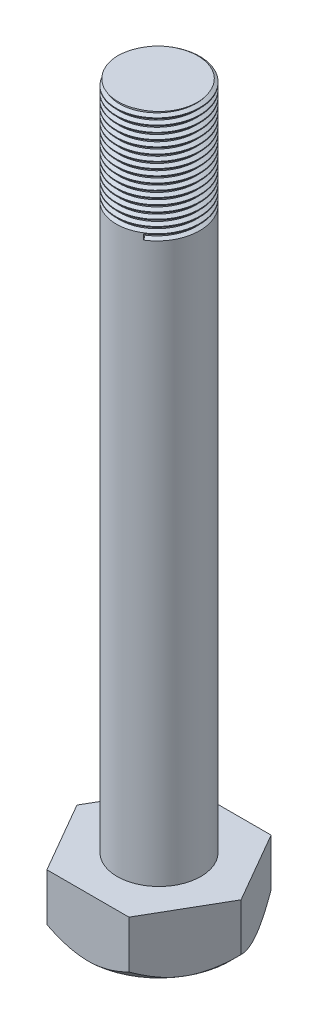
SolidWorks part; units mm, degrees
material "1.0143 (S275J0)"
ref_plane "Front Plane" through (0, 0, 0) normal (0, 0, 1) x (1, 0, 0)
ref_plane "Top Plane" through (0, 0, 0) normal (0, 1, 0) x (1, 0, 0)
ref_plane "Right Plane" through (0, 0, 0) normal (1, 0, 0) x (0, 0, -1)
sketch "Sketch1" plane through (0, 0, 0) normal (0, 1, 0) x (1, 0, 0)
  circle A0 centre (0, 0) radius 10
  dimension "D1" = 20
extrude "Boss-Extrude1" add sketch "Sketch1" along normal blind 160
sketch "Sketch2" plane through (0, 0, 0) normal (0, -1, 0) x (1, 0, 0)
  line L1 (19.6299, 0) -> (9.815, 17)
  line L2 (9.815, 17) -> (-9.815, 17)
  line L3 (-9.815, 17) -> (-19.6299, 0)
  line L4 (-19.6299, 0) -> (-9.815, -17)
  line L5 (-9.815, -17) -> (9.815, -17)
  line L6 (9.815, -17) -> (19.6299, 0)
  circle A0 centre (0, 0) radius 17 construction
  dimension "D1" = 34
extrude "Boss-Extrude2" add sketch "Sketch2" along normal blind 14
sketch "Sketch4" plane through (0, -14, 0) normal (0, -1, 0) x (1, 0, 0)
  circle A0 centre (0, 0) radius 17
extrude "Cut-Extrude1" cut sketch "Sketch4" against normal blind 14 draft 45 flip side to cut
thread "Thread1" pitch 1.5 method cut profile "Thread Profile1" start angle 0, offset 3, length 28, pitch 1.5, diameter 20
ref_plane "Plane1" through (-10, 163, 0) normal (0, 0, 1) x (-1, 0, 0)
sketch "Thread Profile1" plane through (-10, 163, 0) normal (0, 0, 1) x (-1, 0, 0)
  line L0 (0, 0) -> (0, 1.5) construction
  line L11 (0, 0) -> (0, 1.3125)
  line L12 (0, 1.3125) -> (-0.8119, 0.8437)
  line L13 (-0.8119, 0.8437) -> (-0.8119, 0.4687)
  line L15 (-0.8119, 0.4687) -> (0, 0)
  line L17 (-0.8119, 0.6562) -> (0, 0.6562) construction
  point P2 (0, 0)
  dimension "Pitch" = 1.5
  dimension "Profile_Angle" = 60
  dimension "Profile_Land" = 0.375
  dimension "Profile_Height" = 0.8119
